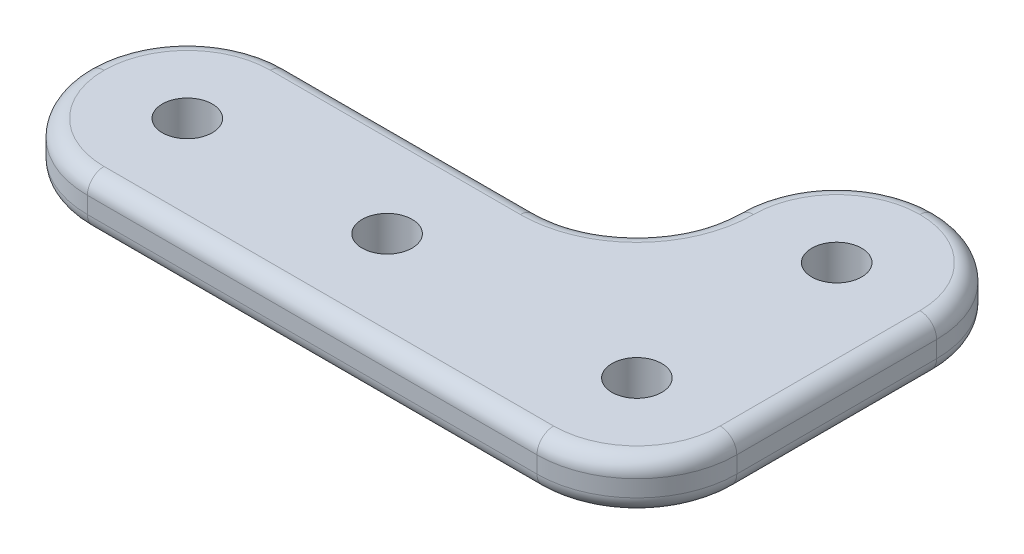
SolidWorks part; units mm, degrees
material "6061 Alloy"
ref_plane "Front Plane" through (0, 0, 0) normal (0, 0, 1) x (1, 0, 0)
ref_plane "Top Plane" through (0, 0, 0) normal (0, 1, 0) x (1, 0, 0)
ref_plane "Right Plane" through (0, 0, 0) normal (1, 0, 0) x (0, 0, -1)
sketch "Sketch1" plane through (0, 0, 0) normal (0, 1, 0) x (1, 0, 0)
  line L0 (0, 25.4) -> (0, -25.4) construction
  line L1 (-12.7, -25.4) -> (12.7, -25.4) construction
  line L2 (-12.7, -25.4) -> (-12.7, 25.4) construction
  line L3 (-12.7, 25.4) -> (12.7, 25.4)
  line L4 (12.7, -25.4) -> (12.7, 25.4) construction
  line L5 (-12.7, -25.4) -> (12.7, 25.4) construction
  line L6 (-12.7, 25.4) -> (12.7, -25.4) construction
  line L7 (-12.7, 0) -> (-69.85, 0)
  line L8 (-69.85, 0) -> (-69.85, -25.4)
  line L9 (-69.85, -25.4) -> (-12.7, -25.4)
  line L10 (-69.85, -12.7) -> (0, -12.7)
  line L11 (-12.7, -25.4) -> (0, -25.4)
  line L12 (12.7, -12.7) -> (12.7, 25.4)
  line L13 (-12.7, 0) -> (-12.7, 25.4)
  circle A1 centre (0, -12.7) radius 3.175
  circle A2 centre (0, 12.7) radius 3.175
  circle A4 centre (0, -12.7) radius 12.7
  circle A5 centre (-57.15, -12.7) radius 3.175
  circle A6 centre (-31.75, -12.7) radius 3.175
  point P0 (0, 0)
  dimension "D3" = 6.35
  dimension "D1" = 25.4
  dimension "D8" = 12.7
  dimension "D6" = 31.75
  dimension "D2" = 25.4
  dimension "D4" = 25.4
  dimension "D5" = 90
  dimension "D7" = 12.7
  dimension "D9" = 25.4
extrude "Boss-Extrude1" add sketch "Sketch1" along normal blind 6.35 contours A5 L10 A4 L12 L3 L13 L7 L8 A2 | A4 A1 | A5 L10 L8 L9 L11 A4 region at (0, 0, -24.4908) region at (8.7263, 0, 21.4263) region at (-39.6451, 0, 19.4343)
fillet "Fillet2" radius 12.7 5 edges at (12.7, 3.175, -25.4) (-12.7, 3.175, -25.4) (-69.85, 3.175, 0) (-69.85, 3.175, 25.4) (-12.7, 3.175, 0)
fillet "Fillet3" radius 2.1167 18 edges at (-8.9803, 0, -21.6803) (8.9803, 0, -21.6803) (12.7, 0, 0) (8.9803, 0, 21.6803) (-28.575, 0, 25.4) (-66.1303, 0, 21.6803) (-66.1303, 0, 3.7197) (-8.9803, 6.35, -21.6803) (8.9803, 6.35, -21.6803) (12.7, 6.35, 0) (8.9803, 6.35, 21.6803) (-28.575, 6.35, 25.4) (-66.1303, 6.35, 21.6803) (-66.1303, 6.35, 3.7197) (-41.275, 0, 0) (-41.275, 6.35, 0) (-16.4197, 0, -3.7197) (-16.4197, 6.35, -3.7197)
